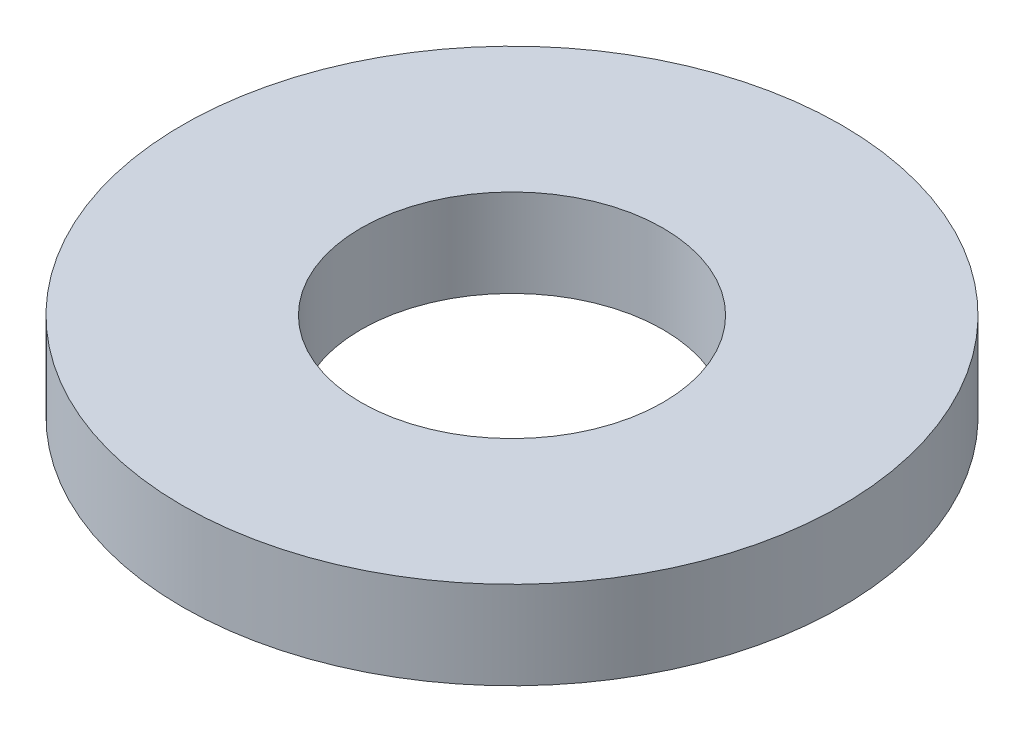
SolidWorks part; units mm, degrees
ref_plane "Front Plane" through (0, 0, 0) normal (0, 0, 1) x (1, 0, 0)
ref_plane "Top Plane" through (0, 0, 0) normal (0, 1, 0) x (1, 0, 0)
ref_plane "Right Plane" through (0, 0, 0) normal (1, 0, 0) x (0, 0, -1)
sketch "Sketch1" plane through (0, 0, 0) normal (0, 1, 0) x (1, 0, 0)
  circle A0 centre (0, 0) radius 60
  dimension "FLANGE_OD" = 120
extrude "Boss-Extrude1" add sketch "Sketch1" along normal blind 16
sketch "Sketch2" plane through (0, 0, 0) normal (0, 1, 0) x (1, 0, 0)
  circle A0 centre (0, 0) radius 27.5
  dimension "BORE_D" = 55
extrude "Cut-Extrude1" cut sketch "Sketch2" along normal through all
sketch "Sketch3" plane through (0, 16, 0) normal (0, 1, 0) x (1, 0, 0)
  circle A0 centre (0, 0) radius 22.9863 construction
  circle A1 centre (-22.9863, 0) radius 1.8097
  dimension "BOLT_D" = 3.6195
  dimension "BOLT_PCD" = 45.9727
extrude "Cut-Extrude2" cut sketch "Sketch3" against normal blind 10.6001 rebuild error yes
pattern_circular "CirPattern1" count 5 over 360 rebuild error yes
